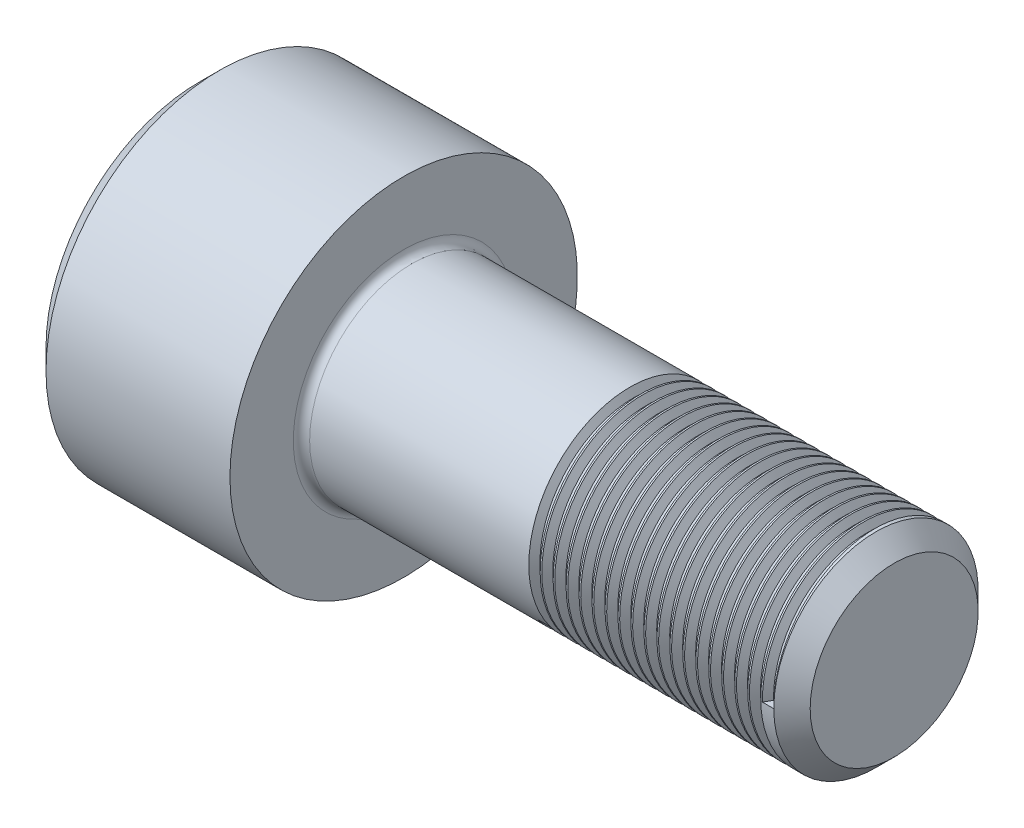
SolidWorks part; units mm, degrees
revolve "Base-Revolve" add sketch "BodySke"
sketch "BodySke" plane through (0, 0, 0) normal (0, 0, 1) x (1, 0, 0)
  line L0 (0, 0) -> (0, 3.75)
  line L1 (0.5, 4.25) -> (5, 4.25)
  line L2 (5, 4.25) -> (5, 2.5)
  line L3 (5, 2.5) -> (16.555, 2.5)
  line L4 (17, 2.055) -> (17, 0)
  line L5 (17, 0) -> (0, 0)
  line L6 (-31.75, 0) -> (127, 0) construction
  line L7 (0, 3.75) -> (0.5, 4.25)
  line L8 (17, 2.055) -> (16.555, 2.5)
  line L9 (0, -3.75) -> (0.5, -4.25) construction
  line L10 (17, -2.055) -> (16.555, -2.5) construction
  line L11 (5.8, 9.525) -> (5.8, 3.175) construction
  line L12 (5, 9.525) -> (5, 3.175) construction
  line L13 (-33, 9.525) -> (-33, 3.175) construction
  dimension "Diameter" = 5
  dimension "Head_ht" = 5
  dimension "Length" = 12
  dimension "Body_ch_ang" = 45
  dimension "Head_dia" = 8.5
  dimension "Head_ch_ang" = 45
  dimension "Minor_dia" = 4.11
  dimension "Advance" = 0.8
  dimension "Thread_nom" = 12
  dimension "Thread_length" = 50
  dimension "Head_ch_ht" = 0.5
cosmetic thread "ThreadCosmetic" [suppressed]
fillet "Fillet1" radius 0.2 1 edges at (5, 0, 2.5)
ref_plane "Plane1" through (0, 0, 0) normal (0, 0, 1) x (1, 0, 0)
ref_plane "Plane2" through (0, 0, 0) normal (0, 1, 0) x (1, 0, 0)
ref_plane "Plane3" through (0, 0, 0) normal (1, 0, 0) x (0, 0, -1)
sketch "Sketch2" plane through (0, 0, 0) normal (0, 0, 1) x (1, 0, 0)
  line L0 (0, 2.042) -> (2.5, 2.042)
  line L1 (2.5, 2.042) -> (3.6789, 0)
  line L2 (-31.75, 0) -> (127, 0) construction
  line L3 (3.6789, 0) -> (0, 0)
  line L4 (0, 0) -> (0, 2.042)
  line L5 (0, 3.75) -> (0, -3.75) construction
  line L6 (0, 0) -> (47.625, 0) construction
  line L7 (5, -4.25) -> (5, 4.25) construction
  dimension "D1" = 2.042
  dimension "D2" = 60
revolve "Hex-PreBroach" cut sketch "Sketch2" angle 360 about L6
sketch "Sketch3" plane through (0, 0, 0) normal (-1, 0, 0) x (0, 0.5, 0.866)
  line L0 (1.1789, 2.042) -> (-1.1789, 2.042)
  line L1 (-1.1789, 2.042) -> (-2.3579, 0)
  line L2 (1.1789, 2.042) -> (2.3579, 0)
  line L3 (1.1789, -2.042) -> (2.3579, 0)
  line L4 (1.1789, -2.042) -> (-1.1789, -2.042)
  line L5 (-1.1789, -2.042) -> (-2.3579, 0)
  dimension "D1" = 2.042
  dimension "D2" = 2.042
extrude "Hex" cut sketch "Sketch3" against normal blind 2.5
sketch "Sketch4" plane through (0, 0, 0) normal (-1, 0, 0) x (0, 0, 1)
  line L0 (0, 0) -> (2.3876, 0)
  line L1 (0, 0) -> (6.1484, 3.5498) construction
  line L2 (0, 0) -> (1.1938, 2.0677)
  line L3 (1.9883, 0.576) -> (2.2704, 0.7389)
  line L4 (1.493, 1.4339) -> (1.7751, 1.5968)
  arc A0 (1.9883, 0.576) -> (1.493, 1.4339) centre (0, 0) ccw
  arc A1 (2.3876, 0) -> (2.2704, 0.7389) centre (0, 0) ccw
  arc A2 (1.1938, 2.0677) -> (1.7751, 1.5968) centre (0, 0) cw
  dimension "D1" = 30
  dimension "D2" = 60
  dimension "Spline_p_dim" = 0.9906
  dimension "D3" = 0.4953
extrude "Spline" [suppressed] cut sketch "Sketch4" against normal blind 2.5
pattern_circular "CirPattern1" [suppressed] count 6 every 60
sketch "Sketch5" plane through (0, 0, 0) normal (0, 0, 1) x (1, 0, 0)
  line L0 (-31.75, 0) -> (127, 0) construction
  line L2 (0, 3.75) -> (0, -3.75) construction
  circle A0 centre (2, 0) radius 0.675
  dimension "Drilled_hole_dia" = 1.35
  dimension "Drilled_hole_loc" = 2
extrude "Hole" [suppressed] cut sketch "Sketch5" against normal through all and the other way through all
pattern_circular "Drilled-4" [suppressed] count 2 every 60
pattern_circular "Drilled-6" [suppressed] count 3 every 60
sketch "ThdSchSke" plane through (0, 0, 0) normal (0, 0, 1) x (1, 0, 0)
  line L0 (5.8, -2.055) -> (5.4884, -2.5)
  line L1 (5.8, -2.055) -> (6.1116, -2.5)
  line L2 (6.1116, -2.5) -> (6.1116, -3.125)
  line L3 (-3.175, 0) -> (5.1513, 0) construction
  line L5 (6.1116, -3.125) -> (5.4884, -3.125)
  line L6 (5.4884, -3.125) -> (5.4884, -2.5)
  line L7 (0, 3.75) -> (0, -3.75) construction
  dimension "Thread_minor" = 4.11
  dimension "Diameter" = 5
  dimension "Start" = 5.8
revolve "ThreadSchematic" [suppressed] cut sketch "ThdSchSke" angle 360 about L3
pattern_linear "ThdSchPat" [suppressed]
thread "Rosca1" pitch 0.3175 method cut profile "Perfil da rosca1" start angle 0, offset 0, length 6, pitch 0.3175, diameter 5
ref_plane "Plano1" through (16.555, 0, 2.5) normal (0, -1, 0) x (0, 0, 1)
sketch "Perfil da rosca1" plane through (16.555, 0, 2.5) normal (0, -1, 0) x (0, 0, 1)
  line L0 (0, 0) -> (0, 0.3175) construction
  line L11 (0, 0) -> (0, 0.2778)
  line L12 (0, 0.2778) -> (-0.1719, 0.1786)
  line L13 (-0.1719, 0.1786) -> (-0.1719, 0.0992)
  line L15 (-0.1719, 0.0992) -> (0, 0)
  line L17 (-0.1719, 0.1389) -> (0, 0.1389) construction
  point P2 (0, 0)
  dimension "Pitch" = 0.3175
  dimension "Profile_Angle" = 60
  dimension "Profile_Land" = 0.0794
  dimension "Profile_Height" = 0.1719
equation "\"D2@Sketch3\" = \"Hex_size@Sketch3\" / 2"
equation "\"D1@Sketch3\" = \"Hex_size@Sketch3\" / 2"
equation "\"D1@Sketch2\" = \"Hex_size@Sketch3\" / 2"
equation "\"D3@Sketch4\" = \"Spline_p_dim@Sketch4\" / 2"
equation "\"Thread_minor@ThreadCosmetic\"  =  \"Minor_dia@BodySke\""
equation "\"D2@CirPattern1\" = 360 / \"Num_teeth@CirPattern1\""
equation "\"Wall_thickness@Sketch2\" = \"Head_ht@BodySke\" - \"Key_eng@Hex\""
equation "\"Thread_length@ThreadCosmetic\" = ((sgn( (\"Length@BodySke\" - \"Advance@BodySke\" ) - \"Thread_nom@BodySke\" )-1)*( (\"Length@BodySke\" - \"Advance@BodySke\" ) - \"Thread_nom@BodySke\" ))/-2+ \"Thread_nom@BodySke\""
equation "\"Thread_minor@ThdSchSke\" = \"Minor_dia@BodySke\""
equation "\"Diameter@ThdSchSke\" = \"Diameter@BodySke\""
equation "\"Overcut@ThdSchSke\" = \"Diameter@BodySke\" * 1.25"
equation "\"Start@ThdSchSke\" = \"Head_ht@BodySke\" + \"Length@BodySke\" - \"Thread_length@ThreadCosmetic\"  '---Non-countersunk---"
equation "\"Num_threads@ThdSchPat\" = int( \"Thread_length@ThreadCosmetic\" / \"Advance@BodySke\" + 0.999 )  + 1"
equation "\"Advance@ThdSchPat\" = \"Thread_length@ThreadCosmetic\" /  (\"Num_threads@ThdSchPat\" - 1) 'relax it"
equation "\"Num_threads@ThdSchPat\" = \"Num_threads@ThdSchPat\" - sgn( \"Num_threads@ThdSchPat\" - 1) '---chamfered tips only---"
